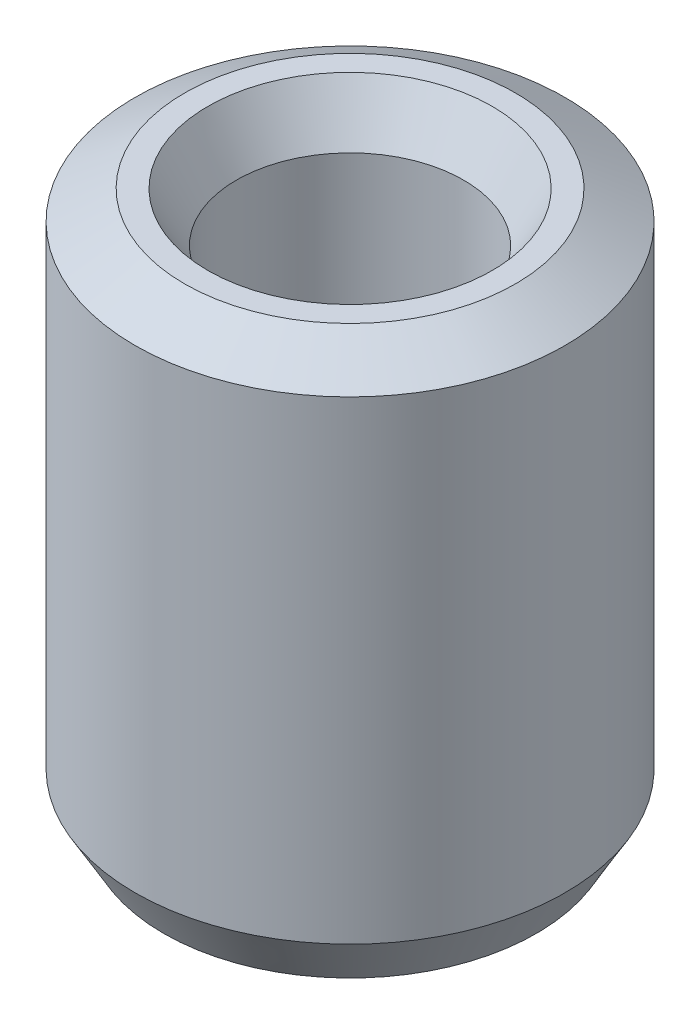
SolidWorks part; units mm, degrees
ref_plane "Front Plane" through (0, 0, 0) normal (0, 0, 1) x (1, 0, 0)
ref_plane "Top Plane" through (0, 0, 0) normal (0, 1, 0) x (1, 0, 0)
ref_plane "Right Plane" through (0, 0, 0) normal (1, 0, 0) x (0, 0, -1)
sketch "Sketch1" plane through (0, 0, 0) normal (0, 1, 0) x (1, 0, 0)
  circle A0 centre (0, 0) radius 10
  dimension "SLEEVE_OD" = 20
extrude "Boss-Extrude1" add sketch "Sketch1" along normal blind 25.6827
sketch "Sketch2" plane through (0, 0, 0) normal (0, 1, 0) x (1, 0, 0)
  circle A0 centre (0, 0) radius 5.285
  dimension "BORE_D" = 10.57
extrude "Cut-Extrude1" cut sketch "Sketch2" along normal through all
chamfer "Chamfer1" distance 1.3303 angle 60 4 edges at (0, 25.6827, 5.285) (0, 0, 5.285) (0, 0, 10) (0, 25.6827, 10) first distance on face at (0, 25.6827, 5.285) first distance on face at (0, 0, 5.285) first distance on face at (0, 25.6827, 10)
